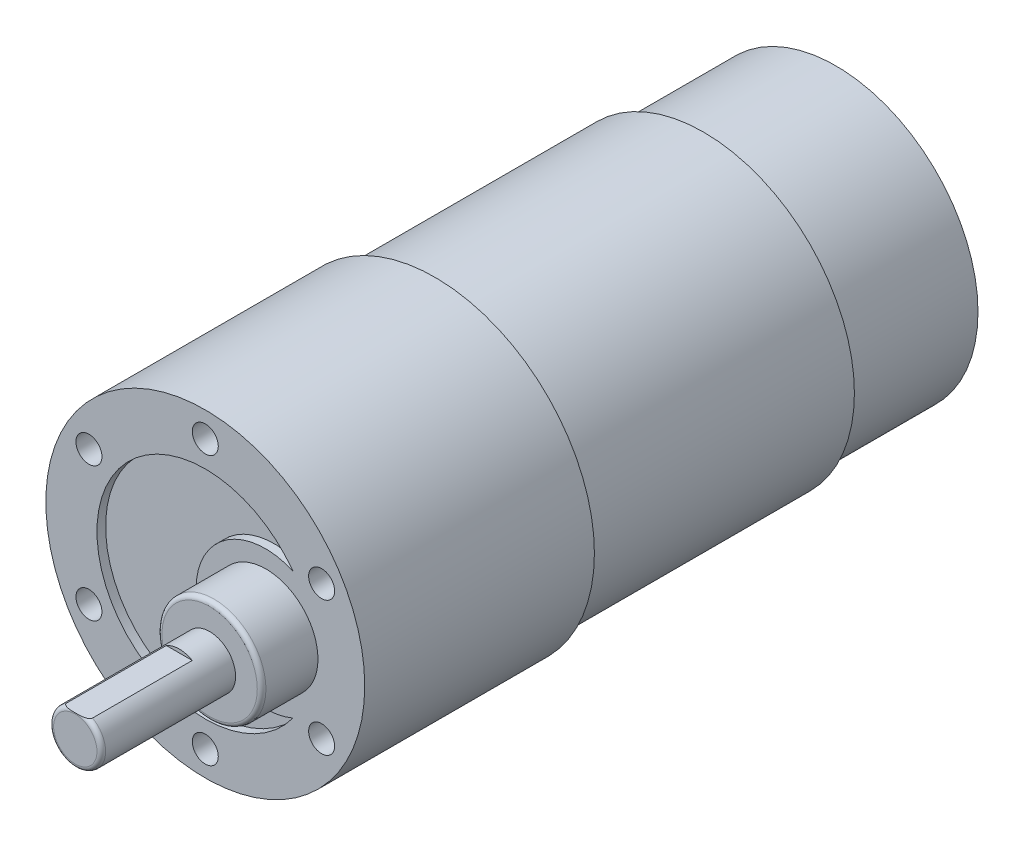
SolidWorks part; units mm, degrees
ref_plane "Front Plane" through (0, 0, 0) normal (0, 0, 1) x (1, 0, 0)
ref_plane "Top Plane" through (0, 0, 0) normal (0, 1, 0) x (1, 0, 0)
ref_plane "Right Plane" through (0, 0, 0) normal (1, 0, 0) x (0, 0, -1)
sketch "Sketch1" plane through (0, 0, 0) normal (0, 0, 1) x (1, 0, 0)
  circle A0 centre (0, 0) radius 18.4
  dimension "D1" = 36.8
extrude "Boss-Extrude1" add sketch "Sketch1" along normal blind 26.5
sketch "Sketch2" plane through (0, 0, 0) normal (0, 0, -1) x (-1, 0, 0)
  circle A0 centre (0, 0) radius 17.4
  dimension "D1" = 34.8
extrude "Boss-Extrude2" add sketch "Sketch2" along normal blind 31
sketch "Sketch3" plane through (0, 0, 26.5) normal (0, 0, 1) x (1, 0, 0)
  circle A0 centre (7, 0) radius 6
  dimension "D1" = 12
  dimension "D2" = 7
extrude "Boss-Extrude3" add sketch "Sketch3" along normal blind 6.5
fillet "Fillet1" radius 0.5 1 edges at (13, 0, 33)
sketch "Sketch4" plane through (0, 0, 33) normal (0, 0, 1) x (1, 0, 0)
  line L0 (7, -6.8172) -> (7, 7.1125) construction
  circle A0 centre (7, 0) radius 3
  dimension "D1" = 6
extrude "Boss-Extrude4" add sketch "Sketch4" along normal blind 15.5
sketch "Sketch5" plane through (0, 0, 48.5) normal (0, 0, 1) x (1, 0, 0)
  line L0 (5.5033, 2.6) -> (8.4967, 2.6)
  line L1 (7, -3) -> (9.3109, -3) construction
  circle A0 centre (7, 0) radius 3 construction
  circle A1 centre (7, 0) radius 3 construction
  arc A2 (8.4967, 2.6) -> (5.5033, 2.6) centre (7, 0) ccw
  dimension "D1" = 5.6
extrude "Cut-Extrude1" cut sketch "Sketch5" against normal blind 12
hole_wizard "Ø3.0 (3) Diameter Hole1" positions "Sketch7" profile "Sketch6" hole size "Ø3.0" standard "Ansi Metric"
sketch "Sketch7" plane through (0, 0, 26.5) normal (0, 0, 1) x (1, 0, 0)
  point P0 (-13.4234, 7.75)
  point P1 (-13.4234, -7.75)
  point P3 (0, -15.5)
  point P5 (13.4234, 7.75)
  point P7 (0, 15.5)
  point P22 (13.4234, -7.75)
  dimension "D1" = 15.5
  dimension "D2" = 15.5
  dimension "D3" = 15.5
  dimension "D4" = 15.5
  dimension "D5" = 15.5
  dimension "D6" = 15.5
  dimension "D7" = 15.5
  dimension "D8" = 15.5
  dimension "D9" = 15.5
  dimension "D10" = 15.5
sketch "Sketch6" plane through (-13.4234, 7.75, 26.5) normal (1, 0, 0) x (0, -1, 0)
  line L0 (0, 0) -> (0, 3.9013)
  line L1 (0, 3.9013) -> (1.5, 3)
  line L2 (1.5, 3) -> (1.5, 0)
  line L5 (1.5, 0) -> (0, 0)
  line L10 (0, 3.9013) -> (-1.5, 3) construction
  line L11 (0, -6.35) -> (0, 107.95) construction
  dimension "Hole Dia." = 3
  dimension "Hole Depth" = 3
  dimension "Drill Angle" = 118
sketch "Sketch8" plane through (0, 0, 26.5) normal (0, 0, 1) x (1, 0, 0)
  line L0 (-0.5907, 0) -> (14.4711, 0) construction
  line L1 (7, 7.3586) -> (7, -7.457) construction
  arc A0 (10.1162, 7.3426) -> (10.1162, -7.3426) centre (0, 0) ccw
  arc A1 (10.1162, 7.3426) -> (10.1162, -7.3426) centre (6.9402, 0) ccw
  dimension "D1" = 25
  dimension "D2" = 16
extrude "Cut-Extrude2" cut sketch "Sketch8" against normal blind 1
sketch "Sketch9" plane through (0, 0, -31) normal (0, 0, -1) x (-1, 0, 0)
  circle A0 centre (0, 0) radius 4
  dimension "D1" = 8
extrude "Boss-Extrude5" add sketch "Sketch9" along normal blind 1
fillet "Fillet2" radius 0.5 1 edges at (-4, 0, -32)
ref_plane "Plane1" through (0, 0, -34) normal (0, 0, -1) x (-1, 0, 0)
sketch "Sketch10" plane through (0, 0, -34) normal (0, 0, -1) x (-1, 0, 0)
  circle A0 centre (0, 0) radius 14
  dimension "D1" = 28
extrude "Boss-Extrude6" add sketch "Sketch10" along normal blind 1.5 separate body
sketch "Sketch11" plane through (0, 0, -31) normal (0, 0, -1) x (-1, 0, 0)
  line L0 (0, 11.55) -> (0, 12.55) construction
  line L1 (-1.75, 12.55) -> (1.75, 12.55)
  line L2 (-1.75, 12.55) -> (-1.75, 11.55)
  line L3 (-1.75, 11.55) -> (1.75, 11.55)
  line L4 (1.75, 12.55) -> (1.75, 11.55)
  line L5 (-1.75, 12.05) -> (1.75, 12.05) construction
  line L6 (-3.5, 0) -> (3.5, 0) construction
  line L7 (1.75, -12.55) -> (1.75, -11.55)
  line L8 (-1.75, -12.55) -> (-1.75, -11.55)
  line L9 (-1.75, -12.55) -> (1.75, -12.55)
  line L10 (-1.75, -11.55) -> (1.75, -11.55)
  circle A0 centre (0, 0) radius 3.5 construction
  dimension "D1" = 3.5
  dimension "D2" = 1
  dimension "D3" = 12.05
extrude "Boss-Extrude7" add sketch "Sketch11" along normal blind 5.6
fillet "Fillet3" radius 0.5 4 edges at (-1.75, -12.05, -36.6) (1.75, -12.05, -36.6) (-1.75, 12.05, -36.6) (1.75, 12.05, -36.6)
ref_plane "Plane2" through (0, 0, -37.5) normal (0, 0, -1) x (-1, 0, 0)
sketch "Sketch13" plane through (0, 0, -37.5) normal (0, 0, -1) x (-1, 0, 0)
  circle A0 centre (0, 0) radius 9
  dimension "D1" = 18
extrude "Boss-Extrude8" add sketch "Sketch13" along normal blind 3 separate body
sketch "Sketch14" plane through (0, 0, -32) normal (0, 0, -1) x (-1, 0, 0)
  circle A0 centre (0, 0) radius 1.5
  dimension "D1" = 3
extrude "Boss-Extrude9" add sketch "Sketch14" along normal blind 8.55
fillet "Fillet4" radius 0.5 1 edges at (7, -3, 48.5)
sketch "Sketch15" plane through (0, 0, -31) normal (0, 0, -1) x (-1, 0, 0)
  circle A0 centre (0, 0) radius 16.4
  circle A1 centre (0, 0) radius 17.4 construction
  dimension "D1" = 1
extrude "Boss-Extrude10" add sketch "Sketch15" along normal blind 15.26
